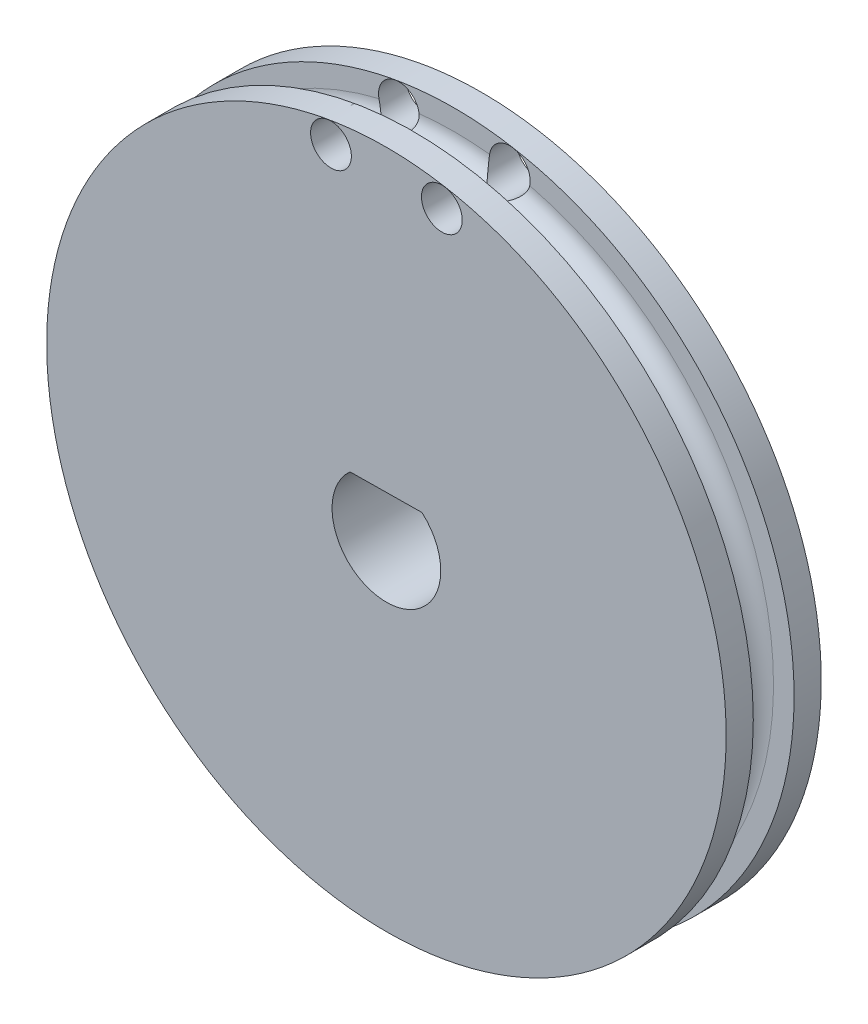
SolidWorks part; units mm, degrees
material "Acrylic (Medium-high impact)"
ref_plane "Front Plane" through (0, 0, 0) normal (0, 0, 1) x (1, 0, 0)
ref_plane "Top Plane" through (0, 0, 0) normal (0, 1, 0) x (1, 0, 0)
ref_plane "Right Plane" through (0, 0, 0) normal (1, 0, 0) x (0, 0, -1)
sketch "Sketch2" plane through (0, 0, 0) normal (1, 0, 0) x (0, 0, -1)
  line L0 (-3.572, 0) -> (3.428, 0)
  line L1 (0, 20.2833) -> (0, -16.4952) construction
  line L2 (-3.572, 0) -> (-3.572, 25)
  line L3 (3.428, 0) -> (3.428, 25)
  line L4 (-3.572, 25) -> (-1.572, 25)
  line L5 (3.428, 25) -> (1.428, 25)
  line L6 (-1.572, 25) -> (-1.572, 23.49)
  line L7 (1.428, 23.49) -> (1.428, 25)
  arc A1 (-1.572, 23.49) -> (1.428, 23.49) centre (-0.072, 23.49) ccw
  dimension "D1" = 7
  dimension "D2" = 25
  dimension "D3" = 2
  dimension "D4" = 2
  dimension "D5" = 25
  dimension "D6" = 1.51
  dimension "D7" = 1.51
revolve "Revolve1" add sketch "Sketch2" angle 360 about L0
sketch "Sketch3" plane through (0, 0, -3.428) normal (0, 0, -1) x (-1, 0, 0)
  line L0 (0, 0) -> (0, 7.3583) construction
  line L1 (-10.3803, 3.1123) -> (10.7938, 2.8836) construction
  line L2 (-2.6132, 3.0284) -> (2.678, 2.9712)
  circle A0 centre (0, 0) radius 4 construction
  arc A1 (-2.6132, 3.0284) -> (2.678, 2.9712) centre (0, 0) ccw
  dimension "D2" = 8
  dimension "D1" = 3
extrude "Cut-Extrude1" cut sketch "Sketch3" against normal blind 9
sketch "Sketch4" plane through (0, 0, -3.428) normal (0, 0, -1) x (-1, 0, 0)
  line L0 (-54.9891, 0) -> (59.117, 0) construction
  line L1 (0, 51.6628) -> (0, 0) construction
  line L2 (0, 0) -> (-9.2544, 52.4842) construction
  line L3 (-9.2544, 52.4842) -> (0, 0) construction
  line L4 (0, 0) -> (9.282, 52.6409) construction
  circle A0 centre (-4.079, 23.1331) radius 1.5
  circle A1 centre (4.079, 23.1331) radius 1.5
  circle A3 centre (0, 0) radius 25 construction
  dimension "D3" = 23.49
  dimension "D1" = 10
  dimension "D2" = 10
  dimension "D4" = 23.49
extrude "Cut-Extrude10" cut sketch "Sketch4" against normal blind 33.49
